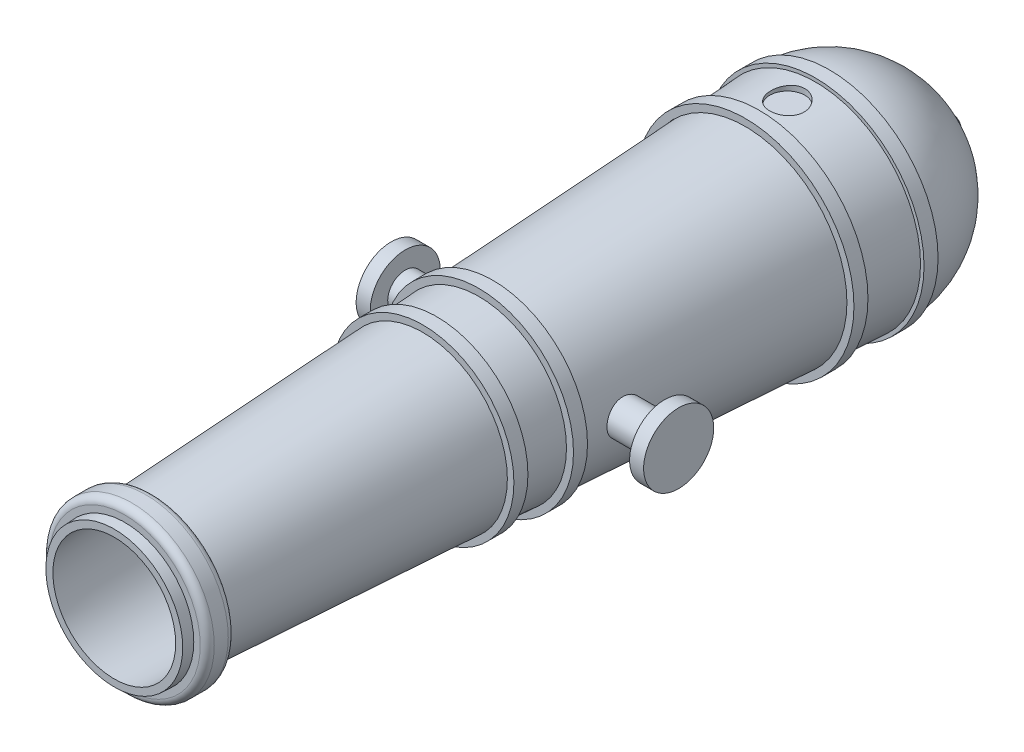
SolidWorks part; units mm, degrees
ref_plane "Front Plane" through (0, 0, 0) normal (0, 0, 1) x (1, 0, 0)
ref_plane "Top Plane" through (0, 0, 0) normal (0, 1, 0) x (1, 0, 0)
ref_plane "Right Plane" through (0, 0, 0) normal (1, 0, 0) x (0, 0, -1)
sketch "Sketch1" plane through (0, 0, 0) normal (0, 0, 1) x (1, 0, 0)
  circle A0 centre (0, 0) radius 190.5
  dimension "D1" = 381
extrude "Boss-Extrude1" add sketch "Sketch1" along normal blind 1270 draft 3
sketch "Sketch5" plane through (0, 0, 0) normal (0, 0, -1) x (-1, 0, 0)
  circle A0 centre (0, 0) radius 190.5
  circle A1 centre (0, 0) radius 190.5 construction
extrude "Boss-Extrude3" add sketch "Sketch5" along normal blind 25.4
sketch "Sketch2" plane through (0, 0, -25.4) normal (0, 0, -1) x (-1, 0, 0)
  line L0 (-249.1509, 0) -> (236.6426, 0) construction
  line L1 (-190.5, 0) -> (190.5, 0)
  arc A0 (-190.5, 0) -> (190.5, 0) centre (0, 0) ccw
  circle A2 centre (0, 0) radius 190.5 construction
revolve "Revolve1" add sketch "Sketch2" angle 180 about L0 reverse direction yes
shell "Shell1" thickness 12.7 removed face at (123.9421, 0, 1270)
ref_plane "Plane1" through (0, 0, -228.6) normal (0, 0, 1) x (1, 0, 0)
sketch "Sketch3" plane through (0, 0, -228.6) normal (0, 0, 1) x (1, 0, 0)
  line L0 (190.5, 0) -> (-190.5, 0) construction
  line L1 (25.4, 0) -> (-25.4, 0)
  arc A0 (-25.4, 0) -> (25.4, 0) centre (0, 0) ccw
  circle A2 centre (0, 0) radius 190.5 construction
  dimension "D1" = 50.8
revolve "Revolve2" add sketch "Sketch3" angle 360 about L0 reverse direction yes
sketch "Sketch4" plane through (0, 0, 0) normal (0, 0, 1) x (1, 0, 0)
  circle A0 centre (0, 0) radius 190.5
  circle A1 centre (0, 0) radius 196.85
  circle A3 centre (0, 0) radius 190.5 construction
  dimension "D1" = 6.35
extrude "Boss-Extrude2" add sketch "Sketch4" against normal blind 25.4 separate body
ref_plane "Plane2" through (0, 0, 1250.95) normal (0, 0, 1) x (1, 0, 0)
sketch "Sketch8" plane through (0, 0, 1250.95) normal (0, 0, 1) x (1, 0, 0)
  circle A0 centre (0, 0) radius 123.9421
  circle A1 centre (0, 0) radius 149.3421
  circle A2 centre (0, 0) radius 123.9421 construction
  dimension "D1" = 25.4
extrude "Boss-Extrude4" add sketch "Sketch8" against normal blind 50.8
fillet "Fillet1" radius 12.7 2 edges at (149.3421, 0, 1200.15) (149.3421, 0, 1250.95)
ref_plane "Plane4" through (0, 0, 127) normal (0, 0, 1) x (1, 0, 0)
sketch "Sketch10" plane through (0, 0, 127) normal (0, 0, 1) x (1, 0, 0)
  circle A0 centre (0, 0) radius 184.15
  circle A1 centre (0, 0) radius 196.85
  dimension "D1" = 368.3
extrude "Boss-Extrude5" add sketch "Sketch10" against normal blind 25.4
ref_plane "Plane5" through (0, 198.12, 0) normal (0, 1, 0) x (1, 0, 0)
sketch "Sketch11" plane through (0, 198.12, 0) normal (0, 1, 0) x (1, 0, 0)
  line L0 (-187.8377, -50.8) -> (187.8377, -50.8) construction
  line L1 (-190.5, 0) -> (-185.1754, -101.6) construction
  line L2 (185.1754, -101.6) -> (190.5, 0) construction
  circle A0 centre (0, -50.8) radius 31.75
  dimension "D1" = 63.5
extrude "Cut-Extrude1" cut sketch "Sketch11" against normal blind 19.05
ref_plane "Plane6" through (0, 0, 711.2) normal (0, 0, 1) x (1, 0, 0)
sketch "Sketch12" plane through (0, 0, 711.2) normal (0, 0, 1) x (1, 0, 0)
  circle A0 centre (0, 0) radius 152.4
  circle A1 centre (0, 0) radius 165.1
  dimension "D1" = 304.8
  dimension "D2" = 12.7
extrude "Boss-Extrude6" add sketch "Sketch12" against normal blind 25.4 contours A1
ref_plane "Plane7" through (0, 0, 609.6) normal (0, 0, 1) x (1, 0, 0)
sketch "Sketch13" plane through (0, 0, 609.6) normal (0, 0, 1) x (1, 0, 0)
  circle A0 centre (0, 0) radius 158.75
  circle A1 centre (0, 0) radius 171.45
  dimension "D1" = 317.5
  dimension "D2" = 12.7
extrude "Boss-Extrude7" add sketch "Sketch13" against normal blind 25.4 contours A1 A0 region at (-166.6007, 0, 609.6)
ref_plane "Plane8" through (171.45, 0, 0) normal (1, 0, 0) x (0, 0, -1)
sketch "Sketch15" plane through (171.45, 0, 0) normal (1, 0, 0) x (0, 0, -1)
  line L0 (0, 0) -> (-1270, 0) construction
  line L1 (-1270, 123.9421) -> (-1270, -123.9421) construction
  circle A0 centre (-508, 0) radius 31.75
  dimension "D1" = 63.5
  dimension "D2" = 508
extrude "Boss-Extrude8" add sketch "Sketch15" along normal blind 63.5 and the other way blind 15.24
sketch "Sketch16" plane through (234.95, 0, 0) normal (1, 0, 0) x (0, 0, -1)
  circle A0 centre (-508, 0) radius 63.5
extrude "Boss-Extrude9" add sketch "Sketch16" along normal blind 25.4
mirror "Mirror1" about plane through (0, 0, 0) normal (1, 0, 0) of "Boss-Extrude9", "Boss-Extrude8"
